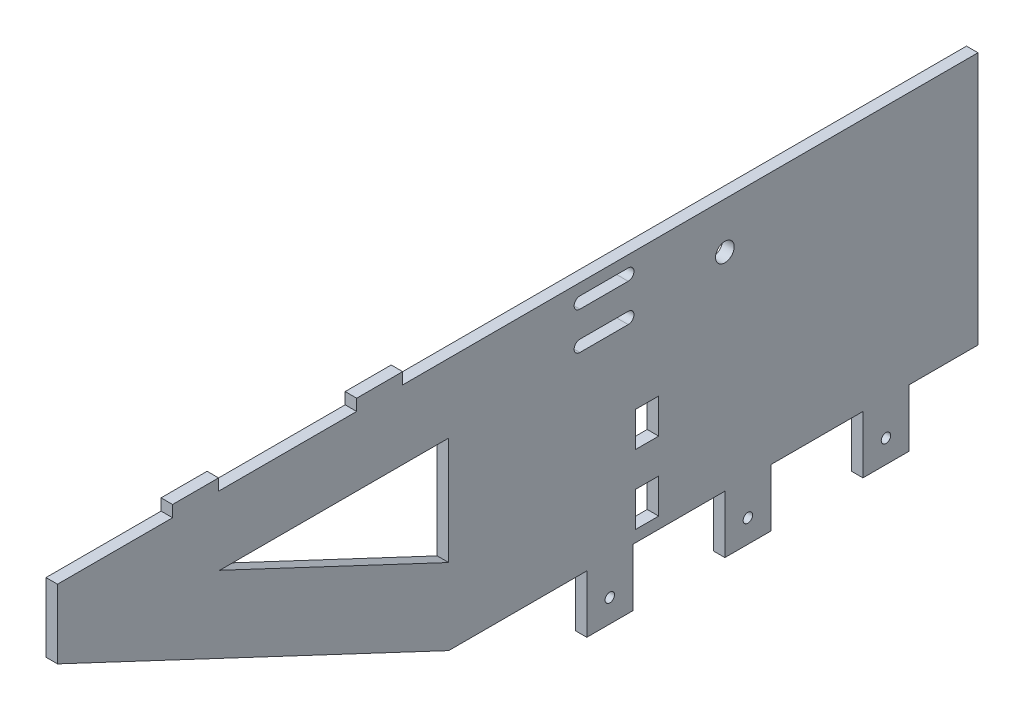
SolidWorks part; units mm, degrees
ref_plane "前基準面" through (0, 0, 0) normal (0, 0, 1) x (1, 0, 0)
ref_plane "上基準面" through (0, 0, 0) normal (0, 1, 0) x (1, 0, 0)
ref_plane "右基準面" through (0, 0, 0) normal (1, 0, 0) x (0, 0, -1)
sketch "草圖1" plane through (0, 0, 0) normal (1, 0, 0) x (0, 0, -1)
  line L1 (100, 55) -> (-100, 55)
  line L2 (100, 55) -> (100, -55)
  line L3 (100, -55) -> (-100, -55)
  line L4 (-100, 55) -> (-100, -55)
  line L5 (0, -55) -> (0, 55) construction
  line L6 (100, 0) -> (-100, 0) construction
  circle A0 centre (-10, 35) radius 4.05
  point P0 (0, 0)
  dimension "D3" = 8.1
  dimension "D1" = 200
  dimension "D2" = 110
  dimension "D4" = 90
  dimension "D5" = 90
extrude "填料-伸長1" add sketch "草圖1" along normal blind 5
sketch "草圖2" plane through (5, 0, 0) normal (1, 0, 0) x (0, 0, -1)
  line L0 (-100, -55) -> (100, -55) construction
  line L1 (-70, -55) -> (-50, -55)
  line L4 (-70, -55) -> (-70, -80)
  line L5 (-70, -80) -> (-50, -80)
  line L6 (-50, -80) -> (-50, -55)
  line L8 (-10, -55) -> (-10, -80)
  line L9 (-10, -80) -> (10, -80)
  line L10 (10, -80) -> (10, -55)
  line L12 (50, -55) -> (50, -80)
  line L13 (50, -80) -> (70, -80)
  line L14 (70, -80) -> (70, -55)
  line L17 (-100, 55) -> (-100, -55) construction
  line L18 (-70, -70) -> (70, -70) construction
  line L19 (-10, -55) -> (10, -55)
  line L20 (50, -55) -> (70, -55)
  line L21 (-70, -60) -> (70, -60) construction
  circle A0 centre (-60, -70) radius 2.05
  circle A1 centre (0, -70) radius 2.05
  circle A2 centre (60, -70) radius 2.05
  point P27 (-60, -80)
  point P30 (60, -80)
  point P32 (0, -55)
  dimension "D7" = 4.1
  dimension "D1" = 25
  dimension "D2" = 30
  dimension "D3" = 40
  dimension "D4" = 40
  dimension "D5" = 20
  dimension "D6" = 5
  dimension "D8" = 10
extrude "填料-伸長2" add sketch "草圖2" against normal blind 5
sketch "草圖3" plane through (5, 0, 0) normal (1, 0, 0) x (0, 0, -1)
  line L0 (-100, -55) -> (100, -55) construction
  line L1 (-100, 55) -> (-100, -55) construction
  line L2 (100, -55) -> (100, 55) construction
  line L4 (-100, 55) -> (-300, 55)
  line L5 (-300, 55) -> (-300, 25)
  line L6 (-300, 25) -> (-130, -55)
  line L7 (-130, -55) -> (-100, -55)
  line L8 (-100, 55) -> (-100, -55)
  line L9 (-130, 25) -> (-130, -21.8442)
  line L10 (-130, -21.8442) -> (-130, -21.8442)
  line L11 (-229.5439, 25) -> (-130, -21.8442)
  line L12 (-229.5439, 25) -> (-229.5439, 25)
  line L13 (-130, 25) -> (-229.5439, 25)
  line L14 (-100, -55) -> (-70, -55) construction
  dimension "D2" = 30
  dimension "D3" = 30
  dimension "D4" = 200
  dimension "D5" = 30
extrude "填料-伸長3" add sketch "草圖3" against normal blind 5
sketch "草圖4" plane through (5, 0, 0) normal (1, 0, 0) x (0, 0, -1)
  line L1 (-48.85, -4.8) -> (-38.75, -4.8)
  line L2 (-48.85, -4.8) -> (-48.85, -19.9)
  line L3 (-48.85, -19.9) -> (-38.75, -19.9)
  line L4 (-38.75, -4.8) -> (-38.75, -19.9)
  line L5 (-48.85, -34.9) -> (-38.75, -34.9)
  line L6 (-48.85, -34.9) -> (-48.85, -50)
  line L7 (-48.85, -50) -> (-38.75, -50)
  line L8 (-38.75, -34.9) -> (-38.75, -50)
  line L10 (-130, -55) -> (-70, -55) construction
  dimension "D1" = 81.15
  dimension "D3" = 10.1
  dimension "D4" = 15
  dimension "D5" = 15.1
  dimension "D6" = 5
extrude "除料-伸長1" cut sketch "草圖4" against normal through all
sketch "草圖5" plane through (0, 55, 0) normal (0, 1, 0) x (1, 0, 0)
  line L0 (0, -130) -> (5, -130) construction
  line L1 (0, -130) -> (5, -130) construction
  line L2 (0, 100) -> (0, -300) construction
  line L3 (0, -150) -> (5, -150)
  line L4 (0, -150) -> (0, -170)
  line L5 (0, -170) -> (5, -170)
  line L6 (5, -150) -> (5, -170)
  line L7 (5, 100) -> (5, -300) construction
  line L9 (0, -230) -> (5, -230)
  line L10 (0, -230) -> (0, -250)
  line L11 (0, -250) -> (5, -250)
  line L12 (5, -230) -> (5, -250)
  dimension "D1" = 20
  dimension "D2" = 60
  dimension "D3" = 20
extrude "填料-伸長4" add sketch "草圖5" along normal blind 5
sketch "草圖6" plane through (5, 0, 0) normal (1, 0, 0) x (0, 0, -1)
  line L0 (-73, 47.5) -> (-52, 47.5) construction
  line L1 (-73, 50) -> (-52, 50)
  line L2 (-73, 45) -> (-52, 45)
  line L3 (-73, 31.2) -> (-52, 31.2) construction
  line L4 (-73, 33.7) -> (-52, 33.7)
  line L5 (-73, 28.7) -> (-52, 28.7)
  line L6 (100, 55) -> (-150, 55) construction
  line L7 (-80, 55) -> (-45, 55) construction
  line L8 (-80, 55) -> (-80, 20) construction
  line L9 (-80, 20) -> (-45, 20) construction
  line L10 (-45, 55) -> (-45, 20) construction
  arc A0 (-73, 50) -> (-73, 45) centre (-73, 47.5) ccw
  arc A1 (-52, 45) -> (-52, 50) centre (-52, 47.5) ccw
  arc A2 (-73, 33.7) -> (-73, 28.7) centre (-73, 31.2) ccw
  arc A3 (-52, 28.7) -> (-52, 33.7) centre (-52, 31.2) ccw
  arc A4 (-73, 50) -> (-73, 45) centre (-73, 47.5) cw construction
  arc A5 (-52, 50) -> (-52, 45) centre (-52, 47.5) ccw construction
  point P2 (-62.5, 47.5)
  point P7 (-62.5, 31.2)
  point P16 (-70.5, 47.5)
  point P19 (-54.5, 47.5)
  point P21 (-62.5, 55)
  dimension "D1" = 5
  dimension "D2" = 16
  dimension "D3" = 11.3
  dimension "D4" = 35
  dimension "D5" = 5
  dimension "D6" = 35
  dimension "D7" = 50
extrude "除料-伸長2" cut sketch "草圖6" against normal through all
